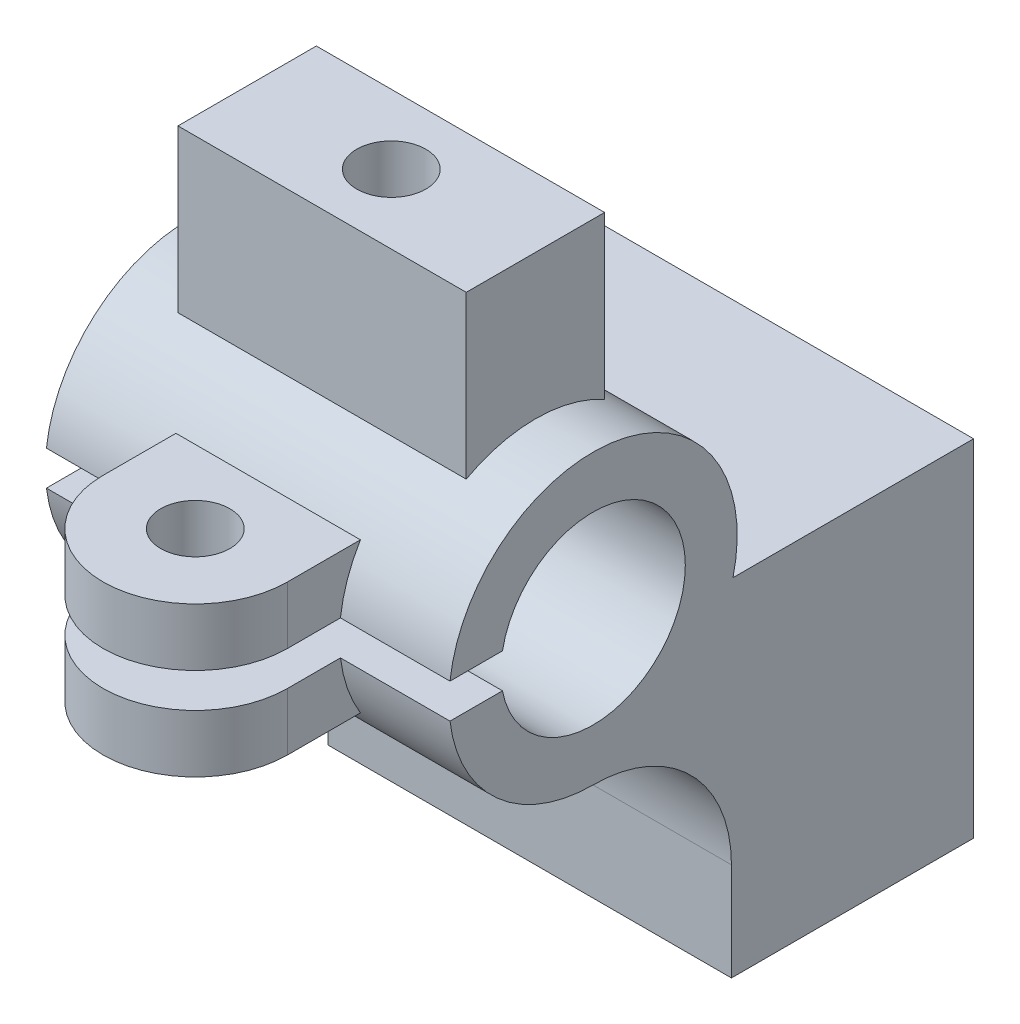
SolidWorks part; units mm, degrees
ref_plane "Front Plane" through (0, 0, 0) normal (0, 0, 1) x (1, 0, 0)
ref_plane "Top Plane" through (0, 0, 0) normal (0, 1, 0) x (1, 0, 0)
ref_plane "Right Plane" through (0, 0, 0) normal (1, 0, 0) x (0, 0, -1)
sketch "Sketch1" plane through (0, 0, 0) normal (1, 0, 0) x (0, 0, -1)
  line L0 (0, 0) -> (0, -16915.4369) construction
  line L1 (1000, 0) -> (-8, 0) construction
  line L2 (33, -3) -> (33, -33)
  line L3 (12, -33) -> (33, -33)
  line L4 (33, -3) -> (12.1347, -3)
  line L5 (12, -33) -> (12, -24.5)
  line L6 (-7.8581, 1.5) -> (-12.4097, 1.5)
  line L7 (6, 25) -> (-6, 25)
  line L8 (6, 25) -> (6, 10.9659)
  line L10 (-6, 25) -> (-6, 10.9659)
  line L11 (0, 11.5898) -> (0, 25) construction
  line L12 (6, 17.9829) -> (-6, 17.9829) construction
  line L13 (-7.8581, -1.5) -> (-12.4097, -1.5)
  line L14 (-10.6771, -6.5) -> (-25, -6.5)
  line L15 (-7.8581, 1.5) -> (-25, 1.5)
  line L17 (-10.6771, 6.5) -> (-25, 6.5)
  line L18 (-25, 1.5) -> (-25, 6.5)
  line L19 (-25, -1.5) -> (-25, -6.5)
  line L20 (-7.8581, -1.5) -> (-25, -1.5)
  arc A0 (-7.8581, -1.5) -> (-7.8581, 1.5) centre (0, 0) ccw
  arc A1 (12.1347, -3) -> (-12.4097, 1.5) centre (0, 0) ccw
  arc A2 (12, -24.5) -> (0, -12.5) centre (0, -24.5) ccw
  arc A3 (-12.4097, -1.5) -> (0, -12.5) centre (0, 0) ccw
  point P3 (0, 17.9829)
  dimension "D1" = 16
  dimension "D2" = 25
  dimension "D7" = 12
  dimension "D3" = 33
  dimension "D4" = 33
  dimension "D5" = 30
  dimension "D6" = 21
  dimension "D8" = 25
  dimension "D9" = 12
  dimension "D10" = 3
  dimension "D11" = 25
  dimension "D12" = 5
extrude "Boss-Extrude1" add sketch "Sketch1" against normal mid plane 35 contours L13 A3 A2 L5 L3 L2 L4 A1 L6 A0 region at (0, -12.5282, -15.394)
extrude "Boss-Extrude2" add sketch "Sketch1<3>" along normal mid plane 25 contours A1 L8 L7 L10 region at (0, 18.493, 0)
sketch "Sketch1<3>" plane through (0, 0, 0) normal (1, 0, 0) x (0, 0, -1) same geometry as "Sketch1"
extrude "Boss-Extrude3" add sketch "Sketch1<4>" along normal mid plane 16 contours A1 L17 L18 L15 | A3 L20 L19 L14 region at (0, 4.0539, 18.3623) region at (0, -4.0539, 18.3623)
sketch "Sketch1<4>" plane through (0, 0, 0) normal (1, 0, 0) x (0, 0, -1) same geometry as "Sketch1"
fillet "Fillet1" 2 edges at (8, 4, 25) (-8, 4, 25) type full round first side face at (8, 4.0232, 18.3386) second side face at (-8, 4.0232, 18.3386) middle face at (0, 4, 25)
fillet "Fillet2" 2 edges at (8, -4, 25) (-8, -4, 25) type full round first side face at (8, -4.0232, 18.3386) second side face at (-8, -4.0232, 18.3386) middle face at (0, -4, 25)
hole_wizard "Ø6.0mm Dowel Hole1" positions "3DSketch2" profile "Sketch2" hole size "Ø6.0" standard "ANSI Metric"
sketch3d "3DSketch2"
  line L0 (0, 1.5, 17) -> (0, 6.5, 17) construction
  point P0 (0, 6.5, 17)
sketch "Sketch2" plane through (0, 6.5, 17) normal (1, 0, 0) x (0, 0, 1)
  line L0 (0, 0) -> (0, 21.0602)
  line L1 (0, 21.0602) -> (3, 21.0602)
  line L2 (3, 21.0602) -> (3, 0)
  line L5 (3, 0) -> (0, 0)
  line L10 (0, 21.0602) -> (-3, 21.0602) construction
  line L11 (0, -6.35) -> (0, 107.95) construction
  dimension "Hole Dia." = 6
  dimension "Hole Depth" = 21.0602
  dimension "Drill Angle" = 180
hole_wizard "Ø6.0mm Dowel Hole2" positions "3DSketch3" profile "Sketch3" hole size "Ø6.0" standard "ANSI Metric"
sketch3d "3DSketch3"
  line L0 (12.5, 25, 6) -> (-12.5, 25, 6) construction
  line L1 (-12.5, 25, -6) -> (-12.5, 25, 6) construction
  point P0 (0, 25, 0)
  dimension "D1" = 6
  dimension "D2" = 12.5
sketch "Sketch3" plane through (0, 25, 0) normal (1, 0, 0) x (0, 0, 1)
  line L0 (0, 0) -> (0, 12)
  line L1 (0, 12) -> (3, 12)
  line L2 (3, 12) -> (3, 0)
  line L5 (3, 0) -> (0, 0)
  line L10 (0, 12) -> (-3, 12) construction
  line L11 (0, -6.35) -> (0, 107.95) construction
  dimension "Hole Dia." = 6
  dimension "Hole Depth" = 12
  dimension "Drill Angle" = 180
